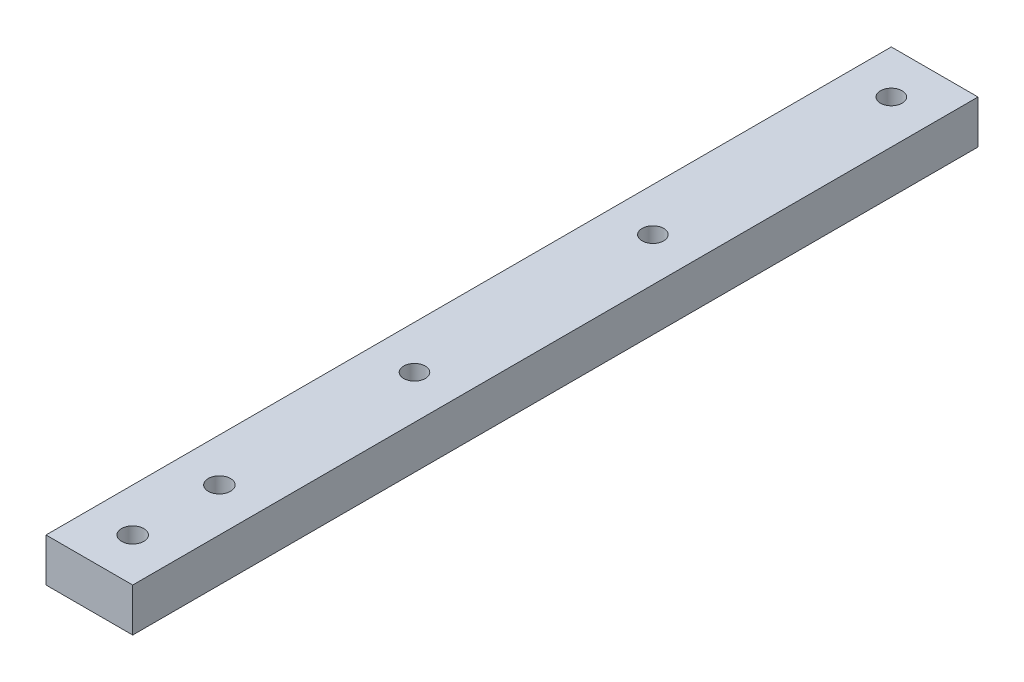
SolidWorks part; units mm, degrees
ref_plane "Front" through (0, 0, 0) normal (0, 0, 1) x (1, 0, 0)
ref_plane "Top" through (0, 0, 0) normal (0, 1, 0) x (1, 0, 0)
ref_plane "Right" through (0, 0, 0) normal (1, 0, 0) x (0, 0, -1)
sketch "Sketch1" plane through (0, 0, 0) normal (0, 0, 1) x (1, 0, 0)
  line L1 (-12.7, -6.35) -> (12.7, -6.35)
  line L2 (-12.7, -6.35) -> (-12.7, 6.35)
  line L3 (-12.7, 6.35) -> (12.7, 6.35)
  line L4 (12.7, -6.35) -> (12.7, 6.35)
  line L5 (-12.7, -6.35) -> (12.7, 6.35) construction
  line L6 (-12.7, 6.35) -> (12.7, -6.35) construction
  point P0 (0, 0)
  dimension "D1" = 12.7
  dimension "D2" = 25.4
extrude "Boss-Extrude1" add sketch "Sketch1" along normal blind 247.65
sketch "Sketch2" plane through (0, 6.35, 0) normal (0, 1, 0) x (1, 0, 0)
  line L0 (0, -247.65) -> (0, -234.95) construction
  line L1 (12.7, -247.65) -> (-12.7, -247.65) construction
  line L2 (0, -234.95) -> (0, -209.55) construction
  line L3 (0, 0) -> (0, -12.7) construction
  line L4 (12.7, 0) -> (-12.7, 0) construction
  line L5 (0, -12.7) -> (0, -82.55) construction
  line L6 (0, -82.55) -> (0, -152.4) construction
  dimension "D1" = 12.7
  dimension "D2" = 25.4
  dimension "D3" = 69.85
  dimension "D4" = 12.7
hole_wizard "1/4 Clearance Hole1" positions "Sketch4" profile "Sketch3" hole size "1/4" standard "ANSI Inch" end condition through all
sketch "Sketch4" plane through (0, 6.35, 0) normal (0, 1, 0) x (1, 0, 0)
  point P0 (0, -234.95)
  point P3 (0, -209.55)
sketch "Sketch3" plane through (0, 6.35, 234.95) normal (1, 0, 0) x (0, 0, 1)
  line L0 (0, 0) -> (0, 12.7)
  line L1 (0, 12.7) -> (3.2639, 12.7)
  line L2 (3.2639, 12.7) -> (3.2639, 0)
  line L5 (3.2639, 0) -> (0, 0)
  line L11 (0, -6.35) -> (0, 107.95) construction
  dimension "Thru Hole Dia." = 6.5278
  dimension "Thru Hole Depth" = 12.7
hole_wizard "1/4 (0.25) Diameter Hole1" positions "Sketch6" profile "Sketch5" hole size "1/4" standard "ANSI Inch" end condition through all
sketch "Sketch6" plane through (0, 6.35, 0) normal (0, 1, 0) x (1, 0, 0)
  point P0 (0, -82.55)
  point P3 (0, -12.7)
  point P6 (0, -152.4)
sketch "Sketch5" plane through (0, 6.35, 82.55) normal (1, 0, 0) x (0, 0, 1)
  line L0 (0, 0) -> (0, 12.7)
  line L1 (0, 12.7) -> (3.175, 12.7)
  line L2 (3.175, 12.7) -> (3.175, 0)
  line L5 (3.175, 0) -> (0, 0)
  line L11 (0, -6.35) -> (0, 107.95) construction
  dimension "Thru Hole Dia." = 6.35
  dimension "Thru Hole Depth" = 12.7
